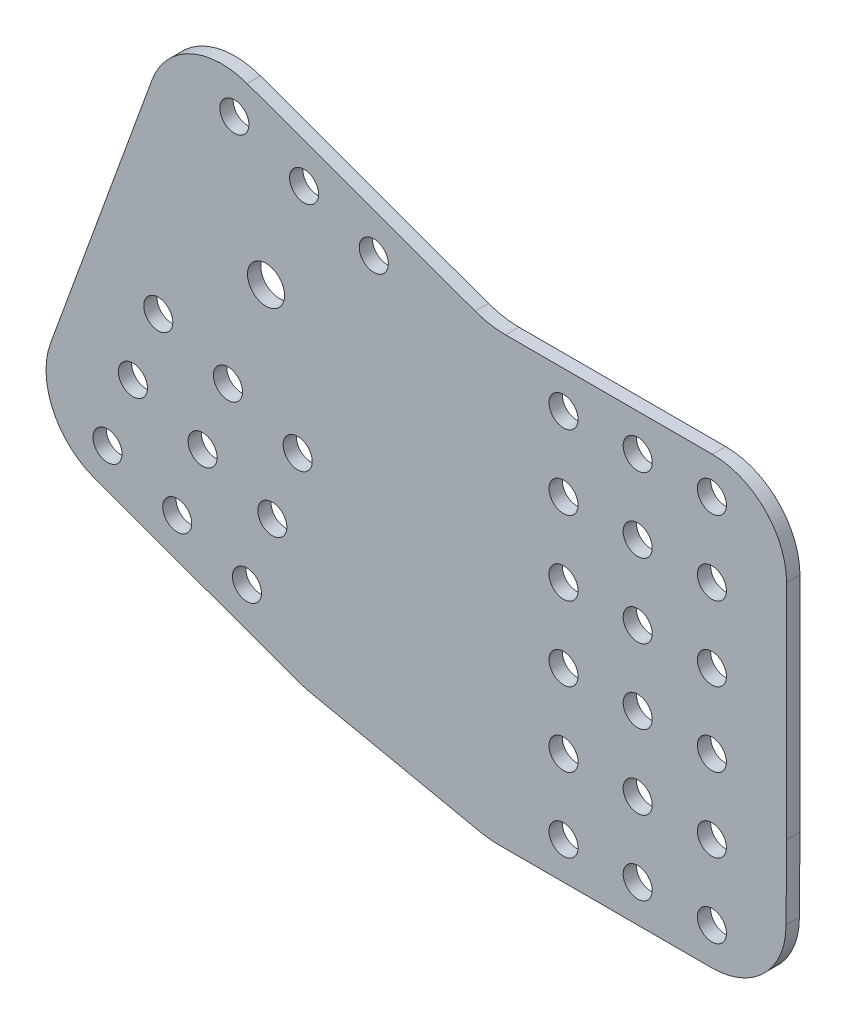
SolidWorks part; units mm, degrees
ref_plane "Front Plane" through (0, 0, 0) normal (0, 0, 1) x (1, 0, 0)
ref_plane "Top Plane" through (0, 0, 0) normal (0, 1, 0) x (1, 0, 0)
ref_plane "Right Plane" through (0, 0, 0) normal (1, 0, 0) x (0, 0, -1)
sketch "Sketch2" plane through (0, 0, 0) normal (0, 0, 1) x (1, 0, 0)
  line L0 (33.4302, 610.9533) -> (33.4302, 560.1533)
  line L1 (33.4302, 610.9533) -> (-17.3698, 610.9533)
  line L2 (-17.3698, 610.9533) -> (-70.8829, 630.4304)
  line L3 (-70.8829, 630.4304) -> (-88.2575, 582.694)
  line L4 (-88.2575, 582.694) -> (-40.5211, 565.3194)
  line L5 (-40.5211, 565.3194) -> (-17.3698, 560.1533)
  line L6 (-17.3698, 560.1533) -> (33.4302, 560.1533)
  line L7 (-70.8829, 630.4304) -> (-76.8499, 632.6022)
  line L8 (-76.8499, 632.6022) -> (-94.2245, 584.8659)
  line L9 (-94.2245, 584.8659) -> (-88.2575, 582.694)
  line L10 (-17.3698, 610.9533) -> (-17.3698, 560.1533)
  line L11 (-40.5211, 565.3194) -> (-23.1465, 613.0558)
  line L12 (33.4302, 610.9533) -> (39.7802, 610.9533)
  line L13 (39.7802, 610.9533) -> (39.7802, 560.1533)
  line L14 (39.7802, 560.1533) -> (33.4302, 560.1533)
  line L15 (-88.2575, 582.694) -> (-92.6011, 570.7599)
  line L16 (-66.5392, 642.3645) -> (-275.0347, 69.5279) construction
  line L17 (-92.6011, 570.7599) -> (-44.8648, 553.3853)
  line L18 (-18.8028, 624.9899) -> (-227.2983, 52.1533) construction
  line L19 (-44.8648, 553.3853) -> (-40.5211, 565.3194)
  line L20 (-17.3698, 560.1533) -> (-17.4643, 547.4533)
  line L21 (-17.4643, 610.9533) -> (-17.4643, -74.8467) construction
  line L22 (-17.4643, 547.4533) -> (33.3357, 547.4533)
  line L23 (33.3357, 610.9533) -> (33.3357, -74.8467) construction
  line L24 (33.3357, 547.4533) -> (33.4302, 560.1533)
  line L25 (-18.8028, 624.9899) -> (-66.5392, 642.3645) construction
  line L26 (-62.2175, 579.9738) -> (-49.1865, 615.7761) construction
  line L27 (-92.6011, 570.7599) -> (-96.9448, 558.8258)
  line L28 (-96.9448, 558.8258) -> (-49.2084, 541.4512)
  line L29 (-49.2084, 541.4512) -> (-44.8648, 553.3853)
  line L30 (-17.4643, 547.4533) -> (-17.4643, 534.7533)
  line L31 (-17.4643, 534.7533) -> (33.3357, 534.7533)
  line L32 (33.3357, 534.7533) -> (33.3357, 547.4533)
  line L33 (-49.2084, 541.4512) -> (-17.4643, 534.7533)
  circle A25 centre (-49.1865, 615.7761) radius 2.4892 construction
  circle A26 centre (-61.1206, 620.1197) radius 2.4892 construction
  circle A27 centre (-49.1865, 615.7761) radius 2.4892
  circle A28 centre (-61.1206, 620.1197) radius 2.4892
  circle A29 centre (-37.2524, 611.4324) radius 2.4892 construction
  circle A30 centre (-50.2834, 575.6301) radius 2.4892 construction
  circle A31 centre (-74.1516, 584.3174) radius 2.4892 construction
  circle A32 centre (-62.2175, 579.9738) radius 2.4892 construction
  circle A33 centre (-54.627, 563.696) radius 2.4892 construction
  circle A34 centre (-66.5611, 568.0397) radius 2.4892 construction
  circle A35 centre (-78.4952, 572.3833) radius 2.4892 construction
  circle A36 centre (-37.2524, 611.4324) radius 2.4892
  circle A37 centre (-50.2834, 575.6301) radius 2.4892
  circle A38 centre (-74.1516, 584.3174) radius 2.4892
  circle A39 centre (-62.2175, 579.9738) radius 2.4892
  circle A40 centre (-54.627, 563.696) radius 2.4892
  circle A41 centre (-66.5611, 568.0397) radius 2.4892
  circle A42 centre (-78.4952, 572.3833) radius 2.4892
  circle A43 centre (-4.7643, 591.9033) radius 2.4892 construction
  circle A44 centre (7.9357, 591.9033) radius 2.4892 construction
  circle A45 centre (20.6357, 591.9033) radius 2.4892 construction
  circle A46 centre (20.6357, 604.6033) radius 2.4892 construction
  circle A47 centre (7.9357, 604.6033) radius 2.4892 construction
  circle A48 centre (-4.7643, 604.6033) radius 2.4892 construction
  circle A49 centre (-4.7643, 591.9033) radius 2.4892
  circle A50 centre (7.9357, 591.9033) radius 2.4892
  circle A51 centre (20.6357, 591.9033) radius 2.4892
  circle A52 centre (20.6357, 604.6033) radius 2.4892
  circle A53 centre (7.9357, 604.6033) radius 2.4892
  circle A54 centre (-4.7643, 604.6033) radius 2.4892
  circle A55 centre (20.6357, 553.8033) radius 2.4892 construction
  circle A56 centre (20.6357, 566.5033) radius 2.4892 construction
  circle A57 centre (7.9357, 566.5033) radius 2.4892 construction
  circle A58 centre (-4.7643, 566.5033) radius 2.4892 construction
  circle A59 centre (-4.7643, 579.2033) radius 2.4892 construction
  circle A60 centre (7.9357, 579.2033) radius 2.4892 construction
  circle A61 centre (20.6357, 579.2033) radius 2.4892 construction
  circle A62 centre (20.6357, 553.8033) radius 2.4892
  circle A63 centre (20.6357, 566.5033) radius 2.4892
  circle A64 centre (7.9357, 566.5033) radius 2.4892
  circle A65 centre (-4.7643, 566.5033) radius 2.4892
  circle A66 centre (-4.7643, 579.2033) radius 2.4892
  circle A67 centre (7.9357, 579.2033) radius 2.4892
  circle A68 centre (20.6357, 579.2033) radius 2.4892
  circle A69 centre (20.6357, 541.1033) radius 2.4892 construction
  circle A70 centre (7.9357, 541.1033) radius 2.4892 construction
  circle A71 centre (-4.7643, 541.1033) radius 2.4892 construction
  circle A72 centre (-58.9707, 551.7619) radius 2.4892 construction
  circle A73 centre (-70.9048, 556.1056) radius 2.4892 construction
  circle A74 centre (-82.8389, 560.4492) radius 2.4892 construction
  circle A75 centre (-4.7643, 553.8033) radius 2.4892 construction
  circle A76 centre (7.9357, 553.8033) radius 2.4892 construction
  circle A77 centre (20.6357, 541.1033) radius 2.4892
  circle A78 centre (7.9357, 541.1033) radius 2.4892
  circle A79 centre (-4.7643, 541.1033) radius 2.4892
  circle A80 centre (-58.9707, 551.7619) radius 2.4892
  circle A81 centre (-70.9048, 556.1056) radius 2.4892
  circle A82 centre (-82.8389, 560.4492) radius 2.4892
  circle A83 centre (-4.7643, 553.8033) radius 2.4892
  circle A84 centre (7.9357, 553.8033) radius 2.4892
  circle A93 centre (-55.702, 597.8749) radius 3.175
  dimension "D3" = 12.7
  dimension "D6" = 12.7
  dimension "D7" = 6.35
  dimension "D8" = 19.05
  dimension "D1" = 50.8
  dimension "D17" = 50.8
  dimension "D18" = 6.35
  dimension "D19" = 6.35
  dimension "D20" = 6.35
  dimension "D21" = 6.35
  dimension "D22" = 50.8
  dimension "D48" = 12.7
  dimension "D49" = 12.7
  dimension "D50" = 12.7
extrude "Boss-Extrude1" add sketch "Sketch2" along normal blind 2.286 contours L4 L11 L2 L3 | L11 L5 L10 L2 | L1 L10 L6 L0 A41 A39 A37 A28 | L17 L19 L4 L15 A54 A52 | L22 L24 L6 L20 | L28 L29 L17 L27 A82 A81 A80 | L31 L32 L22 L30 A79 A78 A77 | L29 L33 L30 L20 L5 L19 region at (8.0396, 585.5533, 0) region at (32.8584, 553.8072, 0) region at (-25.4909, 582.5086, 0) region at (-31.2956, 549.7891, 0) region at (32.8121, 541.1033, 0) region at (-32.6991, 589.5025, 0) region at (-43.2545, 559.5568, 0) region at (-47.5982, 547.6227, 0)
fillet "Fillet6" radius 12.7 4 edges at (-70.8829, 630.4304, 1.143) (-96.9448, 558.8258, 1.143) (33.4302, 610.9533, 1.143) (33.3357, 534.7533, 1.143)
fillet "Fillet7" radius 15.24 3 edges at (-49.2084, 541.4512, 1.143) (-17.4643, 534.7533, 1.143) (-17.3698, 610.9533, 1.143)
